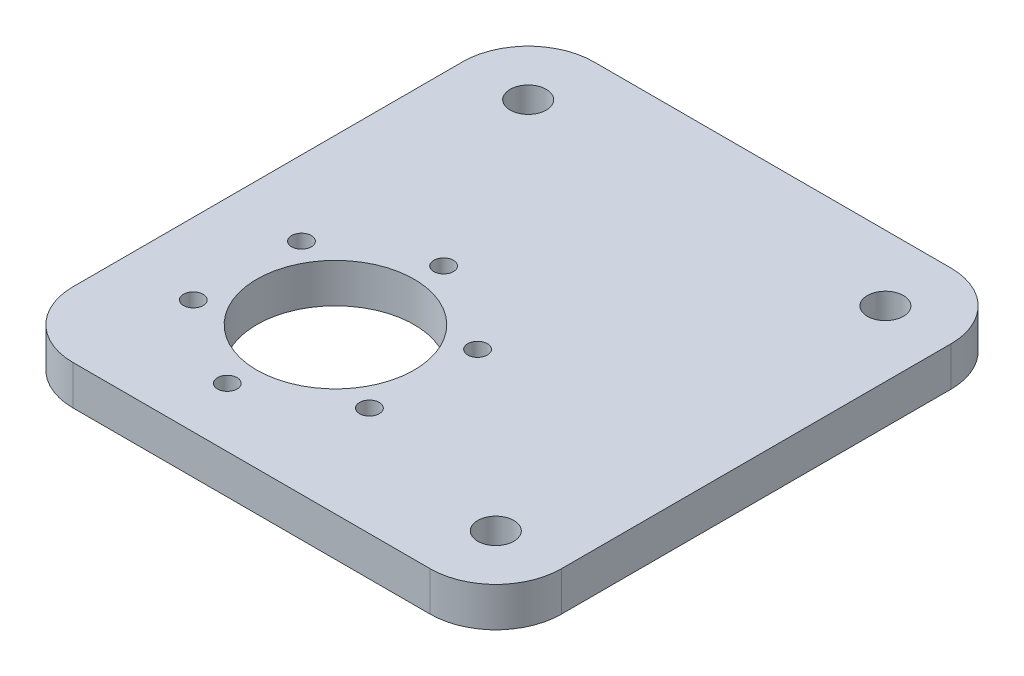
SolidWorks part; units mm, degrees
ref_plane "Front Plane" through (0, 0, 0) normal (0, 0, 1) x (1, 0, 0)
ref_plane "Top Plane" through (0, 0, 0) normal (0, 1, 0) x (1, 0, 0)
ref_plane "Right Plane" through (0, 0, 0) normal (1, 0, 0) x (0, 0, -1)
sketch "Sketch2" plane through (0, 0, 0) normal (0, 1, 0) x (1, 0, 0)
  line L1 (-18.6933, 53.5256) -> (55.7467, 53.5256)
  line L2 (-18.6933, 53.5256) -> (-18.6933, -25.8544)
  line L3 (-18.6933, -25.8544) -> (55.7467, -25.8544)
  line L4 (55.7467, 53.5256) -> (55.7467, -25.8544)
  circle A0 centre (6.3067, -0.8544) radius 12
  dimension "D1" = 24
  dimension "D2" = 74.44
  dimension "D3" = 79.38
extrude "Boss-Extrude1" add sketch "Sketch2" along normal blind 6
sketch "Sketch4" plane through (0, 6, 0) normal (0, 1, 0) x (1, 0, 0)
  circle A0 centre (366.272, -1080.1923) radius 1.25 construction
  circle A1 centre (366.272, -1080.1923) radius 1.25
  circle A2 centre (366.272, -1112.1923) radius 1.25 construction
  circle A3 centre (366.272, -1112.1923) radius 1.25
  circle A4 centre (352.4156, -1104.1923) radius 1.25 construction
  circle A5 centre (352.4156, -1104.1923) radius 1.25
  circle A6 centre (352.4156, -1104.1923) radius 1.25 construction
  circle A7 centre (352.4156, -1104.1923) radius 1.25
  circle A8 centre (352.4156, -1088.1923) radius 1.25 construction
  circle A9 centre (352.4156, -1088.1923) radius 1.25
  circle A10 centre (380.1284, -1088.1923) radius 1.25 construction
  circle A11 centre (380.1284, -1088.1923) radius 1.25
  circle A12 centre (380.1284, -1104.1923) radius 1.25 construction
  circle A13 centre (380.1284, -1104.1923) radius 1.25
sketch "Sketch6" plane through (0, 0, 0) normal (0, -1, 0) x (1, 0, 0)
  line L0 (55.7467, 25.8544) -> (55.7467, -53.5256) construction
  line L1 (55.7467, -53.5256) -> (-18.6933, -53.5256) construction
  line L2 (-18.6933, 25.8544) -> (55.7467, 25.8544) construction
  line L3 (-18.6933, -53.5256) -> (-18.6933, 25.8544) construction
  circle A0 centre (45.7467, 15.8544) radius 2.75
  circle A2 centre (45.7467, -43.5256) radius 2.75
  circle A3 centre (-8.6933, -43.5256) radius 2.75
  dimension "D5" = 5.5
  dimension "D6" = 5.5
  dimension "D7" = 5.5
  dimension "D1" = 10
  dimension "D2" = 10
  dimension "D3" = 10
  dimension "D4" = 10
extrude "Cut-Extrude2" cut sketch "Sketch6" against normal blind 10
sketch "Sketch7" plane through (0, 0, 0) normal (0, -1, 0) x (1, 0, 0)
  circle A0 centre (-7.2956, -7.5704) radius 1.25 construction
  circle A1 centre (-7.2956, -7.5704) radius 1.25
  circle A2 centre (-7.7905, 8.422) radius 1.25 construction
  circle A3 centre (-7.7905, 8.422) radius 1.25
  circle A4 centre (19.9091, 9.2791) radius 1.25 construction
  circle A5 centre (19.9091, 9.2791) radius 1.25
  circle A6 centre (20.4039, -6.7133) radius 1.25 construction
  circle A7 centre (20.4039, -6.7133) radius 1.25
  circle A8 centre (5.8119, 16.8467) radius 1.25 construction
  circle A9 centre (5.8119, 16.8467) radius 1.25
  circle A10 centre (6.8016, -15.138) radius 1.25 construction
  circle A11 centre (6.8016, -15.138) radius 1.25
sketch "Sketch8" plane through (0, 0, 0) normal (0, -1, 0) x (1, 0, 0)
  circle A0 centre (5.8119, 16.8467) radius 1.5
  circle A1 centre (19.9091, 9.2791) radius 1.5
  circle A2 centre (20.4039, -6.7133) radius 1.5
  circle A3 centre (6.8016, -15.138) radius 1.5
  circle A4 centre (-7.2956, -7.5704) radius 1.5
  circle A5 centre (-7.7905, 8.422) radius 1.5
  dimension "D1" = 3
  dimension "D2" = 3
  dimension "D3" = 3
  dimension "D4" = 3
  dimension "D5" = 3
  dimension "D6" = 3
extrude "Cut-Extrude4" cut sketch "Sketch8" against normal through all
fillet "Fillet1" radius 10 4 edges at (55.7467, 3, -53.5256) (-18.6933, 3, -53.5256) (-18.6933, 3, 25.8544) (55.7467, 3, 25.8544)
